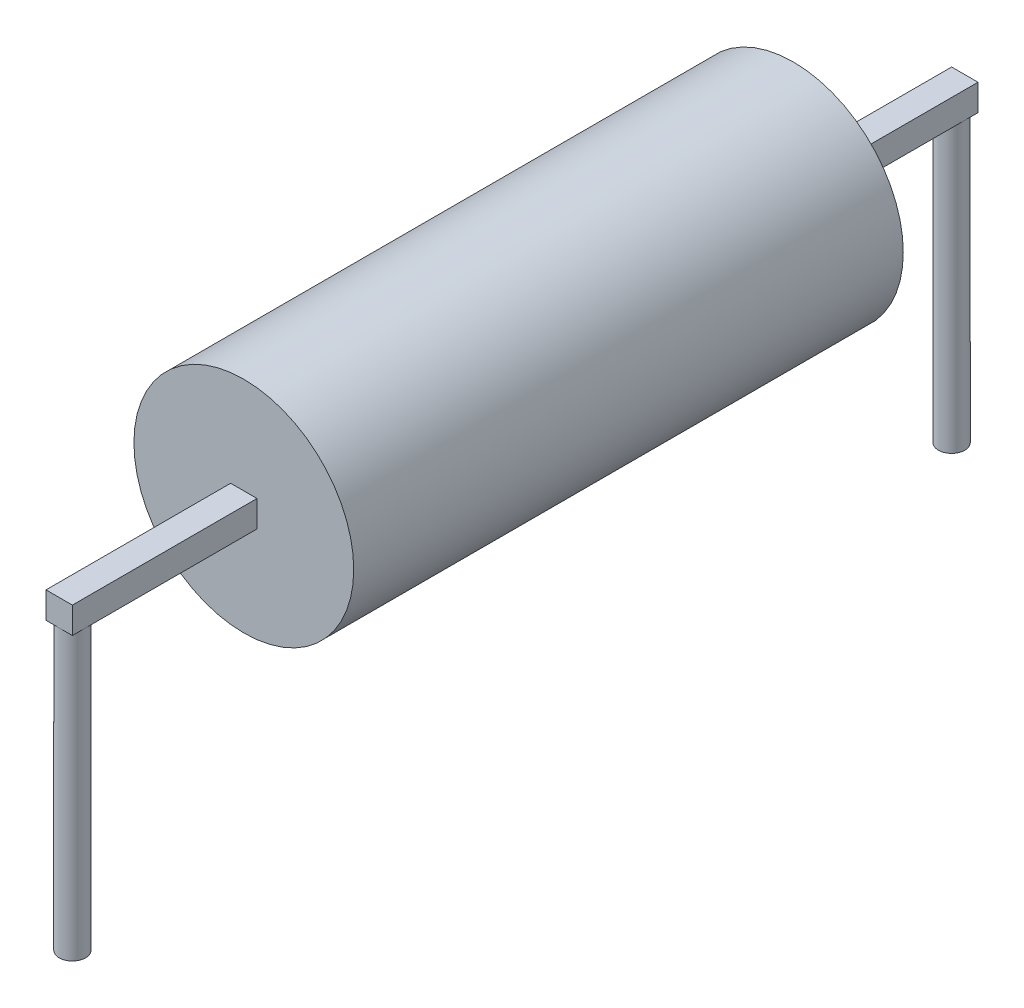
SolidWorks part; units mm, degrees
ref_plane "Спереди" through (0, 0, 0) normal (0, 0, 1) x (1, 0, 0)
ref_plane "Сверху" through (0, 0, 0) normal (0, 1, 0) x (1, 0, 0)
ref_plane "Справа" through (0, 0, 0) normal (1, 0, 0) x (0, 0, -1)
sketch "Эскиз1" plane through (0, 0, 0) normal (0, 0, 1) x (1, 0, 0)
  circle A0 centre (0, 0) radius 2.5
  dimension "D1" = 5
extrude "Вытянуть1" add sketch "Эскиз1" along normal blind 12.5
sketch "Эскиз2" plane through (0, 0, 12.5) normal (0, 0, 1) x (1, 0, 0)
  line L0 (0, 0.6747) -> (0, -0.3959) construction
  line L1 (-0.3, -0.3) -> (0.3, -0.3)
  line L2 (-0.3, -0.3) -> (-0.3, 0.3)
  line L3 (-0.3, 0.3) -> (0.3, 0.3)
  line L4 (0.3, -0.3) -> (0.3, 0.3)
  line L5 (-0.474, 0) -> (0.6636, 0) construction
  dimension "D2" = 0.6
extrude "Вытянуть2" add sketch "Эскиз2" along normal blind 4.2 and the other way blind 16.4
sketch "Эскиз3" plane through (0, -0.3, 0) normal (0, -1, 0) x (1, 0, 0)
  line L0 (0, 12.5) -> (0, 0) construction
  line L1 (-0.3, 16.7) -> (0.3, 16.7) construction
  line L2 (-0.3, -3.9) -> (0.3, -3.9) construction
  circle A0 centre (0, 16.4) radius 0.3
  circle A1 centre (0, -3.6) radius 0.3
  dimension "D1" = 0.6
extrude "Вытянуть3" add sketch "Эскиз3" along normal blind 6.5
